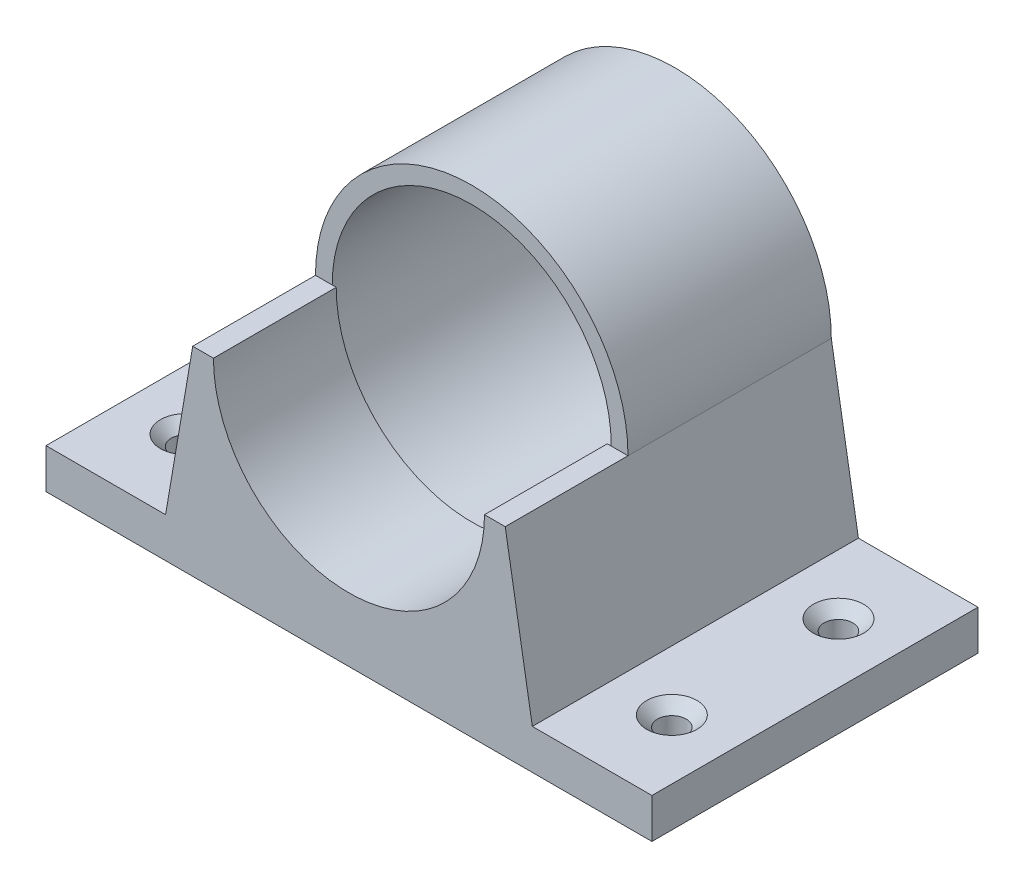
SolidWorks part; units mm, degrees
note: The reader was unsure of these and kept them because the rebuilt part matched: shared geometry of "Sketch1<15>", "Sketch1<19>".
ref_plane "Front Plane" through (0, 0, 0) normal (0, 0, 1) x (1, 0, 0)
ref_plane "Top Plane" through (0, 0, 0) normal (0, 1, 0) x (1, 0, 0)
ref_plane "Right Plane" through (0, 0, 0) normal (1, 0, 0) x (0, 0, -1)
sketch "Sketch1" plane through (0, 0, 0) normal (0, 0, 1) x (1, 0, 0)
  line L0 (-23, -1.8466) -> (-38, -1.8466)
  line L6 (-38, -1.8466) -> (-38, -6.8466)
  line L7 (23, -1.8466) -> (38, -1.8466)
  line L9 (0, 0) -> (0, 18.1534)
  line L12 (38, -1.8466) -> (38, -6.8466)
  line L13 (-23, -1.8466) -> (-19.6, 18.1534)
  line L14 (19.6, 18.1534) -> (23, -1.8466)
  line L15 (-38, -6.8466) -> (38, -6.8466)
  line L16 (-19.6, 18.1534) -> (-17, 18.1534)
  line L17 (17, 18.1534) -> (19.6, 18.1534)
  circle A2 centre (0, 18.1534) radius 17.5
  arc A3 (-19.6, 18.1534) -> (19.6, 18.1534) centre (0, 18.1534) cw
  arc A4 (-19.6, 18.1534) -> (19.6, 18.1534) centre (0, 18.1534) ccw
  arc A6 (17, 18.1534) -> (-17, 18.1534) centre (0, 18.1534) cw
  dimension "D3" = 35
  dimension "D4" = 17
  dimension "D5" = 19.6
  dimension "D1" = 25
  dimension "D2" = 5
  dimension "D7" = 15
  dimension "D8" = 23
extrude "Boss-Extrude9" add sketch "Sketch1" against normal blind 25.5 contours A3 A4 | A2
extrude "Boss-Extrude10" add sketch "Sketch1<15>" against normal blind 25.5 and the other way blind 15.4 contours L13 L0 L6 L15 L12 L7 L14 A4
sketch "Sketch1<15>" plane through (0, 0, 0) normal (0, 0, 1) x (1, 0, 0) same geometry as "Sketch1"
sketch "Sketch8" plane through (0, -1.8466, 0) normal (0, 1, 0) x (1, 0, 0)
  line L0 (-30.5, -15.4) -> (-30.5, -5.4)
  line L1 (-23, -15.4) -> (-38, -15.4) construction
  line L2 (-23, 25.5) -> (-38, 25.5) construction
  line L3 (-30.5, 25.5) -> (-30.5, 15.5)
  line L4 (0, 0) -> (0, 27.9846) construction
  line L5 (30.5, -15.4) -> (30.5, -5.4)
  line L6 (30.5, 25.5) -> (30.5, 15.5)
  dimension "D1" = 10
hole_wizard "CSK for M3 Flat Head Machine Screw1" positions "Sketch11" profile "Sketch10" countersink size "M3" standard "ANSI Metric" end condition through all
sketch "Sketch11" plane through (0, -1.8466, 0) normal (0, 1, 0) x (1, 0, 0)
  point P0 (-30.5, 15.5)
  point P3 (-30.5, -5.4)
sketch "Sketch10" plane through (-30.5, -1.8466, -15.5) normal (1, 0, 0) x (0, 0, 1)
  line L0 (0, 0) -> (0, 5)
  line L1 (0, 5) -> (1.8, 5)
  line L2 (1.8, 5) -> (1.8, 1.35)
  line L3 (1.8, 1.35) -> (3.15, 0)
  line L5 (3.15, 0) -> (0, 0)
  line L6 (-1.8, 1.35) -> (-3.15, 0) construction
  line L11 (0, -6.35) -> (0, 107.95) construction
  dimension "Thru Hole Dia." = 3.6
  dimension "Thru Hole Depth" = 5
  dimension "Near C'Sink Dia." = 6.3
  dimension "Near C'Sink Angle" = 90
hole_wizard "CSK for M3 Flat Head Machine Screw2" positions "Sketch13" profile "Sketch14" countersink size "M3" standard "ANSI Metric" end condition through all
sketch "Sketch13" plane through (0, -1.8466, 0) normal (0, 1, 0) x (1, 0, 0)
  point P0 (30.5, -5.4)
  point P3 (30.5, 15.5)
sketch "Sketch14" plane through (30.5, -1.8466, 5.4) normal (1, 0, 0) x (0, 0, 1)
  line L0 (0, 0) -> (0, 5)
  line L1 (0, 5) -> (1.8, 5)
  line L2 (1.8, 5) -> (1.8, 1.35)
  line L3 (1.8, 1.35) -> (3.15, 0)
  line L5 (3.15, 0) -> (0, 0)
  line L6 (-1.8, 1.35) -> (-3.15, 0) construction
  line L11 (0, -6.35) -> (0, 107.95) construction
  dimension "Thru Hole Dia." = 3.6
  dimension "Thru Hole Depth" = 5
  dimension "Near C'Sink Dia." = 6.3
  dimension "Near C'Sink Angle" = 90
extrude "Boss-Extrude11" add sketch "Sketch1<19>" along normal blind 15.4
sketch "Sketch1<19>" plane through (0, 0, 0) normal (0, 0, 1) x (1, 0, 0) same geometry as "Sketch1"
extrude "Cut-Extrude3" cut sketch "Sketch17" against normal up to surface (4.826 mm away)
sketch "Sketch17" plane through (-499.2489, 9.9746, -84.3089) normal (0.0361, 0.9993, -0.0009) x (0.0508, -0.0009, 0.9987)
  circle A0 centre (67.5, 464.5) radius 1.7
  circle A2 centre (92.5, 462.5) radius 1.8
  circle A3 centre (113.4, 462.5) radius 1.8
  circle A4 centre (92.5, 401.5) radius 1.8
  circle A5 centre (113.4, 401.5) radius 1.8
  circle A7 centre (67.5, 399.5) radius 1.7
  circle A8 centre (44.5, 399.5) radius 1.7
  circle A9 centre (33.5, 468.8378) radius 1.7
  circle A10 centre (33.5, 435.8378) radius 1.7
  circle A11 centre (44.5, 464.5) radius 1.7
